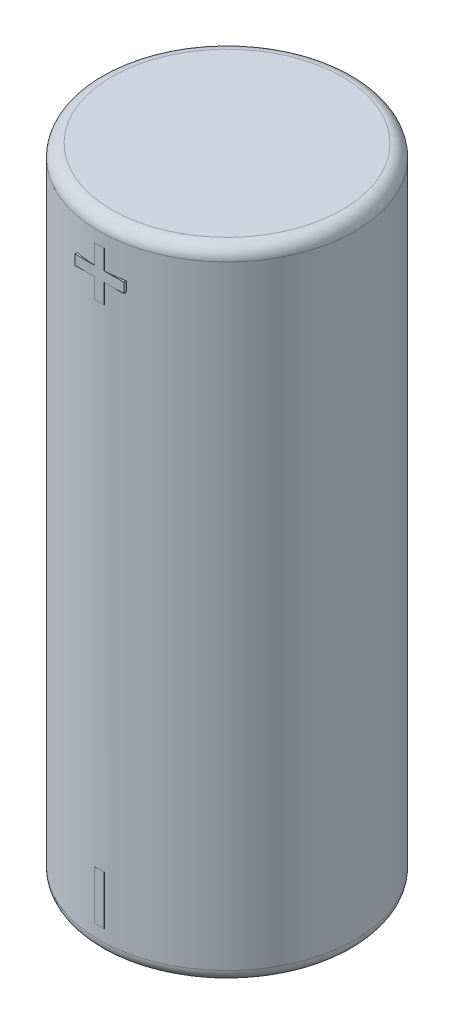
SolidWorks part; units mm, degrees
ref_plane "Front Plane" through (0, 0, 0) normal (0, 0, 1) x (1, 0, 0)
ref_plane "Top Plane" through (0, 0, 0) normal (0, 1, 0) x (1, 0, 0)
ref_plane "Right Plane" through (0, 0, 0) normal (1, 0, 0) x (0, 0, -1)
sketch "Sketch1" plane through (0, 0, 0) normal (0, 1, 0) x (1, 0, 0)
  circle A0 centre (0, 0) radius 13
  dimension "D1" = 26
extrude "Boss-Extrude1" add sketch "Sketch1" along normal blind 65
fillet "Fillet1" radius 1.27 1 edges at (0, 65, 13)
fillet "Fillet2" radius 1.27 1 edges at (0, 0, 13)
ref_plane "Plane1" through (0, 0, 13) normal (0, 0, 1) x (1, 0, 0)
sketch "Sketch2" plane through (0, 0, 13) normal (0, 0, 1) x (1, 0, 0)
  line L0 (11.73, 65) -> (-11.73, 65) construction
  line L1 (11.73, 65) -> (-11.73, 65)
  line L2 (0, 65) -> (0, 0) construction
  line L4 (-0.5, 62.5) -> (0.5, 62.5)
  line L5 (-0.5, 62.5) -> (-0.5, 57.5)
  line L6 (-0.5, 57.5) -> (0.5, 57.5)
  line L7 (0.5, 62.5) -> (0.5, 57.5)
  line L8 (-2.5, 60.5) -> (2.5, 60.5)
  line L9 (-2.5, 60.5) -> (-2.5, 59.5)
  line L10 (-2.5, 59.5) -> (2.5, 59.5)
  line L11 (2.5, 60.5) -> (2.5, 59.5)
  line L12 (-0.5, 7.5) -> (0.5, 7.5)
  line L13 (-0.5, 7.5) -> (-0.5, 2.5)
  line L14 (-0.5, 2.5) -> (0.5, 2.5)
  line L15 (0.5, 7.5) -> (0.5, 2.5)
  point P13 (0, 60)
  point P18 (0, 5)
  dimension "D1" = 5
  dimension "D2" = 5
  dimension "D3" = 1
  dimension "D4" = 1
  dimension "D5" = 0.5
  dimension "D6" = 2.5
  dimension "D7" = 5
  dimension "D8" = 0.5
  dimension "D9" = 2.5
  dimension "D10" = 1
  dimension "D11" = 5
  dimension "D12" = 5
  dimension "D13" = 2.5
  dimension "D14" = 0.5
extrude "Boss-Extrude2" add sketch "Sketch2" against normal blind 10 contours L2 L12 L13 L14 | L12 L2 L14 L15 | L5 L6 L7 L4 | L8 L11 L10 L9 region at (0.25, 5, 13) region at (-0.25, 5, 13)
sketch "Sketch3" plane through (0, 65, 0) normal (0, 1, 0) x (1, 0, 0)
  point P0 (0, 0)
sketch "Sketch4" plane through (0, 0, 0) normal (0, -1, 0) x (-1, 0, 0)
  point P0 (0, 0)
  point P1 (0, 0)
